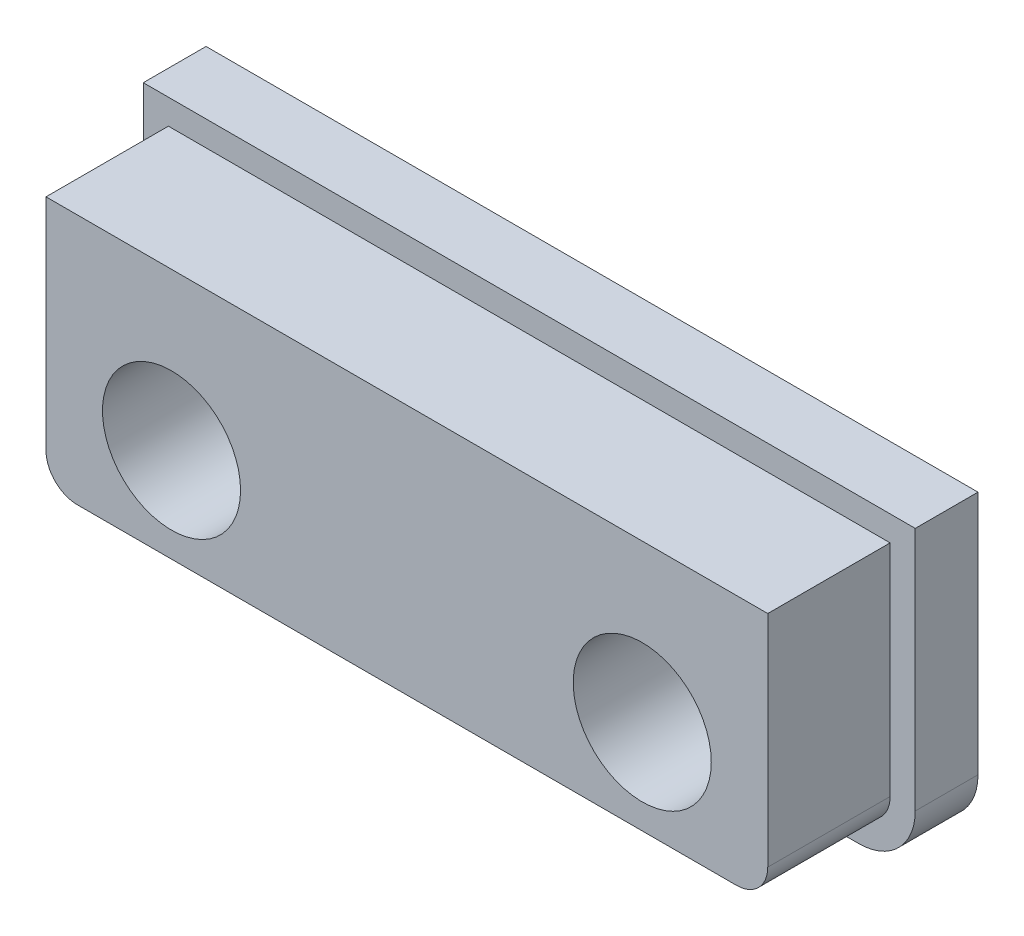
SolidWorks part; units mm, degrees
ref_plane "Front Plane" through (0, 0, 0) normal (0, 0, 1) x (1, 0, 0)
ref_plane "Top Plane" through (0, 0, 0) normal (0, 1, 0) x (1, 0, 0)
ref_plane "Right Plane" through (0, 0, 0) normal (1, 0, 0) x (0, 0, -1)
sketch "Sketch1" plane through (0, 0, 0) normal (0, 0, 1) x (1, 0, 0)
  line L0 (0.2, 7.8) -> (22.8, 7.8)
  line L1 (1, 0) -> (22, 0)
  line L2 (0, 1) -> (0, 8)
  line L3 (0, 8) -> (23, 8)
  line L4 (23, 1) -> (23, 8)
  line L5 (22.8, 1) -> (22.8, 7.8)
  line L6 (1, 0.2) -> (22, 0.2)
  line L7 (0.2, 1) -> (0.2, 7.8)
  line L8 (4, 3) -> (19, 3) construction
  line L9 (-0.8, 1) -> (-0.8, 8.8)
  line L10 (-0.8, 8.8) -> (23.8, 8.8)
  line L11 (23.8, 1) -> (23.8, 8.8)
  line L12 (1, -0.8) -> (22, -0.8)
  arc A0 (22, 0) -> (23, 1) centre (22, 1) ccw
  arc A1 (1, 0) -> (0, 1) centre (1, 1) cw
  arc A2 (22, 0.2) -> (22.8, 1) centre (22, 1) ccw
  arc A3 (1, 0.2) -> (0.2, 1) centre (1, 1) cw
  circle A4 centre (19, 3) radius 2.2
  circle A5 centre (4, 3) radius 2.2
  arc A6 (22, -0.8) -> (23.8, 1) centre (22, 1) ccw
  arc A7 (1, -0.8) -> (-0.8, 1) centre (1, 1) cw
  point P9 (0, 0)
  point P22 (11.5, 7.8)
  point P23 (11.5, 3)
  dimension "D1" = 1
  dimension "D5" = 4.4
  dimension "D6" = 15
  dimension "D7" = 3
  dimension "D2" = 7
  dimension "D3" = 21
  dimension "D4" = 0.2
  dimension "D8" = 0.8
extrude "Boss-Extrude1" add sketch "Sketch1" along normal blind 3.9 contours A3 L6 A2 L5 L0 L7 A5 A4 | A1 L1 A0 L4 L3 L2 L6 A3 L7 L0 L5 A2 region at (11.5, 4.2226, 0) region at (0.3101, 0.3101, 0)
extrude "Boss-Extrude2" add sketch "Sketch1<4>" against normal blind 2 contours A7 L12 A6 L11 L10 L9 L1 A1 L2 L3 L4 A0 | A1 L1 A0 L4 L3 L2 L6 A3 L7 L0 L5 A2 | A3 L6 A2 L5 L0 L7 A5 A4 region at (11.5, 4.2226, 0) region at (0.3101, 0.3101, 0) region at (-0.5359, 4.9, 0)
sketch "Sketch1<4>" plane through (0, 0, 0) normal (0, 0, 1) x (1, 0, 0) same geometry as "Sketch1"
